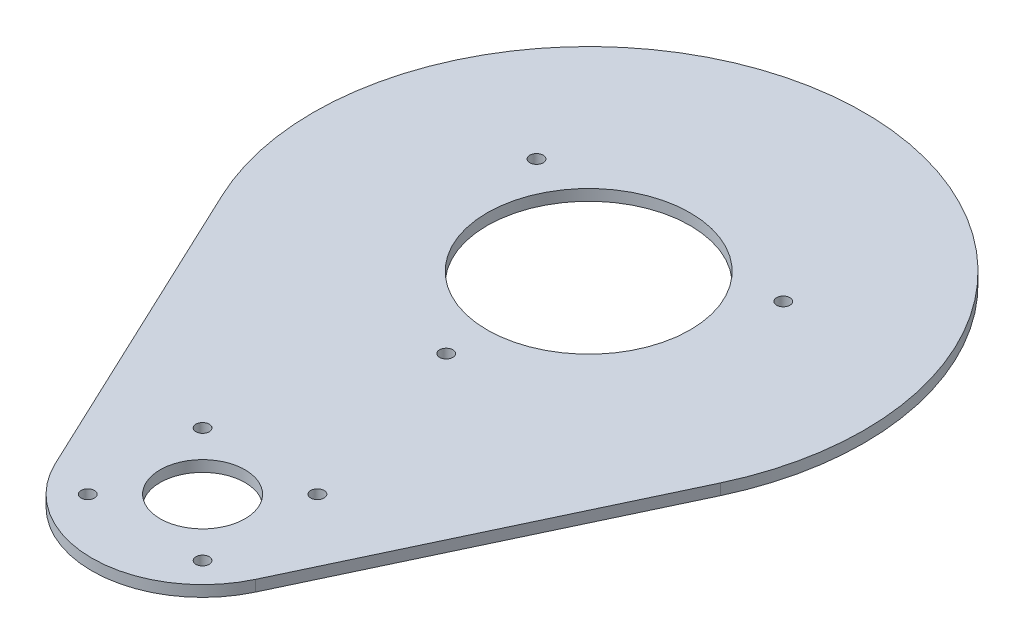
SolidWorks part; units mm, degrees
material "Thornel VCB-20 Carbon Cloth"
ref_plane "Front Plane" through (0, 0, 0) normal (0, 0, 1) x (1, 0, 0)
ref_plane "Top Plane" through (0, 0, 0) normal (0, 1, 0) x (1, 0, 0)
ref_plane "Right Plane" through (0, 0, 0) normal (1, 0, 0) x (0, 0, -1)
ref_plane "Plane1" through (0, 32, 0) normal (0, 1, 0) x (1, 0, 0)
sketch "Sketch1" plane through (0, 32, 0) normal (0, 1, 0) x (1, 0, 0)
  line L0 (75, 84.6375) -> (75, -135.3625) construction
  line L1 (-75, -135.3625) -> (75, -135.3625) construction
  line L2 (-75, 84.6375) -> (75, 84.6375) construction
  line L3 (-75, 84.6375) -> (-75, -135.3625) construction
  line L4 (75, 84.6375) -> (75, -135.3625)
  line L5 (-75, -135.3625) -> (75, -135.3625)
  line L6 (-75, 84.6375) -> (75, 84.6375)
  line L7 (-75, 84.6375) -> (-75, -135.3625)
extrude "Boss-Extrude1" add sketch "Sketch1" along normal blind 3
hole_wizard "Hole1" positions "Sketch2" profile "Sketch3" legacy
sketch "Sketch2" plane through (0, 35, 0) normal (0, 1, 0) x (1, 0, 0)
  point P0 (0, 0)
sketch "Sketch3" plane through (0, 35, 0) normal (1, 0, 0) x (0, 0, 1)
  line L0 (0, 0) -> (0, 100)
  line L1 (0, 100) -> (27.5, 100)
  line L2 (27.5, 100) -> (27.5, 0)
  line L3 (27.5, 0) -> (0, 0)
  line L4 (0, 110) -> (0, -10) construction
  dimension "Diameter" = 55
  dimension "Depth" = 100
hole_wizard "Hole2" positions "Sketch4" profile "Sketch5" legacy
sketch "Sketch4" plane through (0, 35, 0) normal (0, 1, 0) x (1, 0, 0)
  point P0 (0, -104.6)
sketch "Sketch5" plane through (0, 35, 104.6) normal (1, 0, 0) x (0, 0, 1)
  line L0 (0, 0) -> (0, 100)
  line L1 (0, 100) -> (11.5, 100)
  line L2 (11.5, 100) -> (11.5, 0)
  line L3 (11.5, 0) -> (0, 0)
  line L4 (0, 110) -> (0, -10) construction
  dimension "Diameter" = 23
  dimension "Depth" = 100
sketch "Sketch6" plane through (0, 32, 0) normal (0, 1, 0) x (1, 0, 0)
  line L1 (15.5563, -120.1563) -> (-15.5563, -120.1563) construction
  line L2 (15.5563, -120.1563) -> (15.5563, -89.0437) construction
  line L3 (15.5563, -89.0437) -> (-15.5563, -89.0437) construction
  line L4 (-15.5563, -120.1563) -> (-15.5563, -89.0437) construction
  line L5 (15.5563, -120.1563) -> (-15.5563, -89.0437) construction
  line L6 (15.5563, -89.0437) -> (-15.5563, -120.1563) construction
  circle A0 centre (0, -104.6) radius 22 construction
  dimension "D1" = 44
hole_wizard "M3 Clearance Hole1" positions "Sketch7" profile "Sketch9" hole size "M3" standard "ANSI Metric" end condition through all
sketch "Sketch7" plane through (0, 35, 0) normal (0, 1, 0) x (1, 0, 0)
  point P0 (-15.5563, -89.0437)
  point P3 (15.5563, -89.0437)
  point P6 (15.5563, -120.1563)
  point P9 (-15.5563, -120.1563)
sketch "Sketch9" plane through (-15.5563, 35, 89.0437) normal (1, 0, 0) x (0, 0, 1)
  line L0 (0, 0) -> (0, 3)
  line L1 (0, 3) -> (1.8, 3)
  line L2 (1.8, 3) -> (1.8, 0)
  line L5 (1.8, 0) -> (0, 0)
  line L11 (0, -6.35) -> (0, 107.95) construction
  dimension "Thru Hole Dia." = 3.6
  dimension "Thru Hole Depth" = 3
sketch "Sketch10" plane through (0, 32, 0) normal (0, 1, 0) x (1, 0, 0)
  line L0 (-67.4788, -31.8084) -> (-27.1362, -117.3916)
  line L1 (27.1362, -117.3916) -> (67.4788, -31.8084)
  line L6 (75, 84.6375) -> (-75, 84.6375)
  line L7 (-75, 84.6375) -> (-75, -135.3625)
  line L8 (-75, -135.3625) -> (75, -135.3625)
  line L9 (75, -135.3625) -> (75, 84.6375)
  line L10 (75, 84.6375) -> (-75, 84.6375)
  line L11 (-75, 84.6375) -> (-75, -135.3625)
  line L12 (-75, -135.3625) -> (75, -135.3625)
  line L13 (75, -135.3625) -> (75, 84.6375)
  circle A0 centre (0, 0) radius 74.6
  circle A1 centre (0, -104.6) radius 30
  dimension "D1" = 60
  dimension "D2" = 0
extrude "Cut-Extrude3" cut sketch "Sketch10" along normal blind 10 contours L12 L13 L10 L11 A1 L0 A0 L1 region at (72.3373, 32, 25.3625)
sketch "Sketch11" plane through (0, 32, 0) normal (0, 1, 0) x (1, 0, 0)
  circle A0 centre (-33.4286, 19.3) radius 2.6 construction
  circle A1 centre (33.4286, 19.3) radius 2.6 construction
  circle A2 centre (0, -38.6) radius 2.6 construction
  circle A3 centre (-33.4286, 19.3) radius 2.6
  circle A4 centre (33.4286, 19.3) radius 2.6
  circle A5 centre (0, -38.6) radius 2.6
hole_wizard "M3 Clearance Hole2" positions "Sketch12" profile "Sketch13" hole size "M3" standard "ANSI Metric" end condition through all
sketch "Sketch12" plane through (0, 32, 0) normal (0, -1, 0) x (-1, 0, 0)
  point P0 (-33.4286, 19.3)
  point P3 (33.4286, 19.3)
  point P6 (0, -38.6)
sketch "Sketch13" plane through (33.4286, 32, -19.3) normal (1, 0, 0) x (0, 0, -1)
  line L0 (0, 0) -> (0, 3)
  line L1 (0, 3) -> (1.8, 3)
  line L2 (1.8, 3) -> (1.8, 0)
  line L5 (1.8, 0) -> (0, 0)
  line L11 (0, -6.35) -> (0, 107.95) construction
  dimension "Thru Hole Dia." = 3.6
  dimension "Thru Hole Depth" = 3
